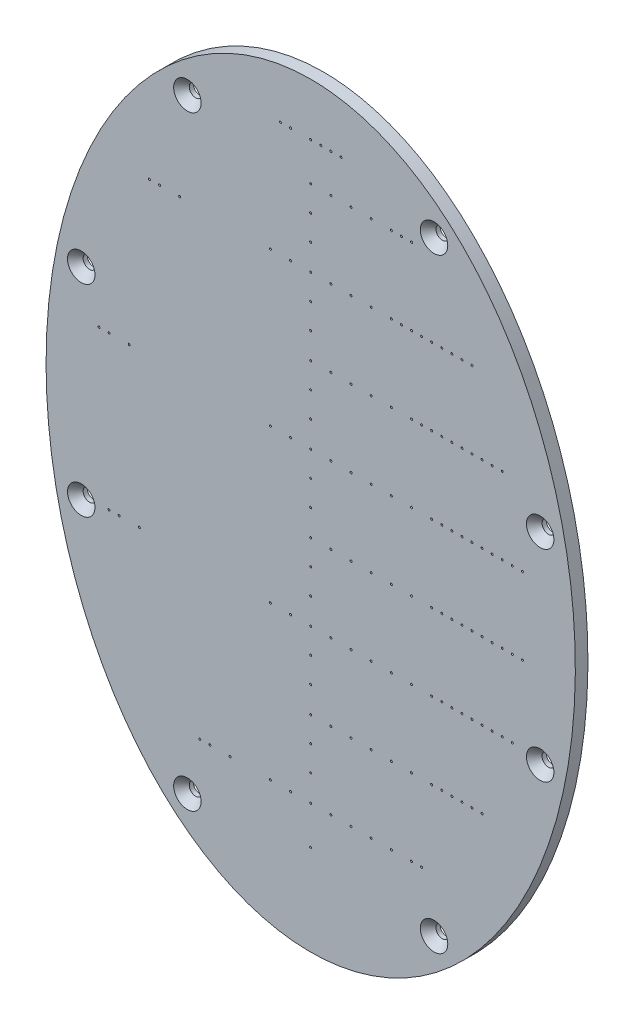
SolidWorks part; units mm, degrees
material "6061 Alloy"
ref_plane "Front Plane" through (0, 0, 0) normal (0, 0, 1) x (1, 0, 0)
ref_plane "Top Plane" through (0, 0, 0) normal (0, 1, 0) x (1, 0, 0)
ref_plane "Right Plane" through (0, 0, 0) normal (1, 0, 0) x (0, 0, -1)
sketch "Sketch2" plane through (0, 0, 0) normal (0, 0, 1) x (1, 0, 0)
  ellipse E0 centre (0, 0) end of major axis (0, 95.25) minor radius 66.675
  dimension "D1" = 190.5
  dimension "D2" = 133.35
extrude "Boss-Extrude1" add sketch "Sketch2" along normal blind 3.175
ref_plane "Plane1" through (0, 130.81, 0) normal (0, 1, 0) x (1, 0, 0)
hole_wizard "CSK for #4 Flat Head Socket Cap Screw1" positions "Sketch4" profile "Sketch3" countersink size "#4" standard "ANSI Inch"
sketch "Sketch4" plane through (0, 0, 3.175) normal (0, 0, 1) x (1, 0, 0)
  line L3 (0, 0) -> (31.0721, 76.2) construction
  ellipse E0 centre (0, 0) end of major axis (0, 88.9) minor radius 60.325
  ellipse E1 centre (0, 0) end of major axis (0, 95.25) minor radius 66.675 construction
  ellipse E2 centre (0, 0) end of major axis (0, 95.25) minor radius 66.675 construction
  point P2 (31.0721, 76.2)
  point P4 (57.8103, 25.4)
  point P13 (31.0721, -76.2)
  point P69 (57.8103, -25.4)
  dimension "D1" = 6.35
  dimension "D2" = 6.35
  dimension "D4" = 25.4
  dimension "D5" = 50.8
sketch "Sketch3" plane through (31.0721, 76.2, 3.175) normal (1, 0, 0) x (0, -1, 0)
  line L0 (0, 0) -> (0, 92.9286)
  line L1 (0, 92.9286) -> (1.6319, 91.948)
  line L2 (1.6319, 91.948) -> (1.6319, 2.1021)
  line L3 (1.6319, 2.1021) -> (3.4593, 0)
  line L5 (3.4593, 0) -> (0, 0)
  line L6 (-1.6319, 2.1021) -> (-3.4593, 0) construction
  line L10 (0, 92.9286) -> (-1.632, 91.948) construction
  line L11 (0, -6.35) -> (0, 107.95) construction
  dimension "Hole Dia." = 3.2639
  dimension "Hole Depth" = 91.948
  dimension "Near C'Sink Dia." = 6.9186
  dimension "Near C'Sink Angle" = 82
  dimension "Drill Angle" = 118
mirror "Mirror1" about plane through (0, 0, 0) normal (1, 0, 0) of "CSK for #4 Flat Head Socket Cap Screw1"
hole_wizard "CBORE for 1/2 Hex Head Bolt1" positions "Sketch8" profile "Sketch9" counterbore size "1/2" standard "ANSI Inch"
sketch "Sketch8" plane through (0, 0, 0) normal (0, 0, -1) x (-1, 0, 0)
  line L3 (0, 72.39) -> (0, 62.738) construction
  line L4 (0, 72.39) -> (0, 82.042) construction
  line L6 (0, 82.042) -> (-62.7225, 82.042) construction
  line L10 (0, 72.39) -> (-68.4113, 72.39) construction
  line L12 (0, 53.086) -> (-75.0551, 53.086) construction
  line L14 (0, 33.782) -> (-81.8919, 33.782) construction
  line L16 (0, 14.478) -> (-86.9631, 14.478) construction
  line L18 (0, -4.826) -> (-81.8919, -4.826) construction
  line L20 (0, -24.13) -> (-60.2195, -24.13) construction
  line L22 (0, -43.434) -> (-66.675, -43.434) construction
  line L24 (0, -62.738) -> (-65.3847, -62.738) construction
  line L25 (-5.08, 14.478) -> (-5.08, -116.9907) construction
  line L27 (-10.16, 14.478) -> (-10.16, -116.9907) construction
  line L29 (-15.24, -116.9907) -> (-15.24, 14.478) construction
  line L31 (-20.32, 14.478) -> (-20.32, -116.9907) construction
  line L33 (-25.4, -116.9907) -> (-25.4, 14.478) construction
  line L37 (-30.48, -116.9907) -> (-30.48, 14.478) construction
  line L39 (-33.02, 14.478) -> (-33.02, -116.9907) construction
  line L41 (-35.56, -116.9907) -> (-35.56, 14.478) construction
  line L43 (-38.1, 14.478) -> (-38.1, -116.9907) construction
  line L45 (-40.64, -116.9907) -> (-40.64, 14.478) construction
  line L47 (-43.18, 14.478) -> (-43.18, -116.9907) construction
  line L49 (-45.72, -116.9907) -> (-45.72, 14.478) construction
  line L51 (-48.26, 14.478) -> (-48.26, -116.9907) construction
  line L53 (-50.8, -116.9907) -> (-50.8, 14.478) construction
  line L55 (-53.34, 14.478) -> (-53.34, -116.9907) construction
  line L56 (0, 72.39) -> (0, 62.738) construction
  ellipse E0 centre (0, 0) end of major axis (0, 76.2) minor radius 57.15 construction
  point P0 (0, 72.39)
  point P37 (0, 53.086)
  point P39 (0, 33.782)
  point P41 (0, 14.478)
  point P43 (0, -4.826)
  point P45 (0, -24.13)
  point P47 (0, -43.434)
  point P49 (0, -62.738)
  point P50 (0, -72.39)
  point P54 (0, 82.042)
  point P109 (-5.08, 82.042)
  point P111 (-7.62, 82.042)
  point P116 (-2.54, 82.042)
  point P117 (-20.32, 72.39)
  point P121 (-15.24, 72.39)
  point P123 (-10.16, 72.39)
  point P125 (-5.08, 72.39)
  point P133 (-22.86, 72.39)
  point P136 (-5.08, 53.086)
  point P138 (-10.16, 53.086)
  point P140 (-15.24, 53.086)
  point P144 (-20.32, 53.086)
  point P146 (-22.86, 53.086)
  point P148 (-25.4, 53.086)
  point P150 (-27.94, 53.086)
  point P153 (-30.48, 53.086)
  point P155 (-33.02, 53.086)
  point P157 (-35.56, 53.086)
  point P160 (-38.1, 53.086)
  point P163 (-10.16, 33.782)
  point P165 (-15.24, 33.782)
  point P167 (-20.32, 33.782)
  point P171 (-25.4, 33.782)
  point P173 (-27.94, 33.782)
  point P175 (-30.48, 33.782)
  point P177 (-33.02, 33.782)
  point P179 (-35.56, 33.782)
  point P181 (-38.1, 33.782)
  point P183 (-40.64, 33.782)
  point P185 (-43.18, 33.782)
  point P187 (-45.72, 33.782)
  point P189 (-48.26, 33.782)
  point P195 (-5.08, 33.782)
  point P198 (-5.08, 14.478)
  point P200 (-10.16, 14.478)
  point P202 (-15.24, 14.478)
  point P204 (-20.32, 14.478)
  point P208 (-25.4, 14.478)
  point P212 (-30.48, 14.478)
  point P214 (-33.02, 14.478)
  point P216 (-35.56, 14.478)
  point P218 (-38.1, 14.478)
  point P220 (-40.64, 14.478)
  point P221 (-43.18, 14.478)
  point P223 (-45.72, 14.478)
  point P225 (-48.26, 14.478)
  point P227 (-50.8, 14.478)
  point P240 (-53.34, 14.478)
  point P287 (-5.08, -4.826)
  point P289 (-10.16, -4.826)
  point P291 (-15.24, -4.826)
  point P293 (-20.32, -4.826)
  point P295 (-25.4, -4.826)
  point P299 (-30.48, -4.826)
  point P301 (-33.02, -4.826)
  point P303 (-35.56, -4.826)
  point P305 (-38.1, -4.826)
  point P306 (-40.64, -4.826)
  point P308 (-43.18, -4.826)
  point P310 (-45.72, -4.826)
  point P312 (-48.26, -4.826)
  point P314 (-50.8, -4.826)
  point P316 (-53.34, -4.826)
  point P331 (-5.08, -24.13)
  point P333 (-10.16, -24.13)
  point P335 (-15.24, -24.13)
  point P336 (-20.32, -24.13)
  point P338 (-25.4, -24.13)
  point P342 (-30.48, -24.13)
  point P344 (-33.02, -24.13)
  point P346 (-35.56, -24.13)
  point P348 (-38.1, -24.13)
  point P350 (-40.64, -24.13)
  point P352 (-43.18, -24.13)
  point P354 (-45.72, -24.13)
  point P356 (-48.26, -24.13)
  point P360 (-50.8, -24.13)
  point P367 (-5.08, -43.434)
  point P369 (-10.16, -43.434)
  point P371 (-15.24, -43.434)
  point P373 (-20.32, -43.434)
  point P375 (-25.4, -43.434)
  point P379 (-30.48, -43.434)
  point P381 (-35.56, -43.434)
  point P383 (-38.1, -43.434)
  point P385 (-40.64, -43.434)
  point P387 (-43.18, -43.434)
  point P395 (-27.94, -62.738)
  point P397 (-25.4, -62.738)
  point P399 (-20.32, -62.738)
  point P401 (-15.24, -62.738)
  point P403 (-10.16, -62.738)
  point P405 (-5.08, -62.738)
  point P408 (-33.02, -43.434)
  point P411 (-40.64, 53.086)
  point P412 (-25.4, 72.39)
  point P422 (7.62, 82.042)
  point P424 (5.08, 82.042)
  point P427 (40.64, 53.086)
  point P429 (33.02, 53.086)
  point P432 (38.1, 53.086)
  point P434 (5.08, 53.086)
  point P436 (10.16, 53.086)
  point P440 (5.08, 14.478)
  point P442 (10.16, 14.478)
  point P444 (53.34, 14.478)
  point P446 (50.8, 14.478)
  point P448 (45.72, 14.478)
  point P453 (5.08, -24.13)
  point P455 (10.16, -24.13)
  point P457 (50.8, -24.13)
  point P459 (48.26, -24.13)
  point P461 (43.18, -24.13)
  point P465 (10.16, -62.738)
  point P467 (5.08, -62.738)
  point P469 (27.94, -62.738)
  point P471 (25.4, -62.738)
  point P473 (20.32, -62.738)
  point P490 (0, 62.738)
  point P491 (0, 43.434)
  point P492 (0, 24.13)
  point P493 (0, 4.826)
  point P494 (0, -14.478)
  point P495 (0, -33.782)
  point P496 (0, -53.086)
  point P500 (0, 66.04)
  point P502 (0, 59.69)
  point P514 (0, 46.736)
  point P515 (0, 40.386)
  point P516 (0, 27.432)
  point P517 (0, 21.082)
  point P518 (0, 8.128)
  point P519 (0, 1.778)
  point P520 (0, -11.176)
  point P521 (0, -17.526)
  point P522 (0, -30.48)
  point P523 (0, -36.83)
  point P524 (0, -49.784)
  point P525 (0, -56.134)
  dimension "D1" = 152.4
  dimension "D2" = 114.3
  dimension "D3" = 72.39
  dimension "D5" = 9.652
  dimension "D7" = 2.54
  dimension "D6" = 2.54
  dimension "D8" = 2.54
  dimension "D12" = 5.08
  dimension "D13" = 5.08
  dimension "D14" = 5.08
  dimension "D15" = 2.54
  dimension "D16" = 5.08
  dimension "D17" = 5.08
  dimension "D18" = 5.08
  dimension "D21" = 2.54
  dimension "D22" = 2.54
  dimension "D23" = 2.54
  dimension "D24" = 2.54
  dimension "D25" = 2.54
  dimension "D26" = 2.54
  dimension "D27" = 2.54
  dimension "D28" = 2.54
  dimension "D29" = 2.54
  dimension "D30" = 2.54
  dimension "D31" = 2.54
  dimension "D32" = 2.54
  dimension "D33" = 2.54
  dimension "D34" = 2.54
  dimension "D35" = 2.54
  dimension "D38" = 5.08
  dimension "D39" = 5.08
  dimension "D40" = 2.54
  dimension "D41" = 5.08
  dimension "D42" = 5.08
  dimension "D43" = 2.54
  dimension "D44" = 2.54
  dimension "D9" = 5.08
  dimension "D45" = 2.54
  dimension "D46" = 2.54
  dimension "D47" = 5.08
  dimension "D48" = 5.08
  dimension "D49" = 5.08
  dimension "D50" = 22.86
  dimension "D51" = 2.54
  dimension "D52" = 5.08
  dimension "D53" = 45.72
  dimension "D54" = 2.54
  dimension "D55" = 5.08
  dimension "D56" = 43.18
  dimension "D57" = 2.54
  dimension "D58" = 5.08
  dimension "D59" = 20.32
  dimension "D60" = 9.652
  dimension "D61" = 6.35
  dimension "D62" = 6.35
  dimension "D64" = 19.304
  dimension "D10" = 5.08
  dimension "D11" = 2.54
  dimension "D19" = 5.08
  dimension "D20" = 2.54
  dimension "D4" = 16
  dimension "D63" = 7
sketch "Sketch9" plane through (0, 72.39, 0) normal (1, 0, 0) x (0, 1, 0)
  line L0 (0, 0) -> (0, 6.5026)
  line L1 (0, 6.5026) -> (0.254, 6.35)
  line L2 (0.254, 6.35) -> (0.254, 1.5875)
  line L3 (0.254, 1.5875) -> (0.508, 1.5875)
  line L4 (0.508, 1.5875) -> (0.508, 0)
  line L5 (0.508, 0) -> (0, 0)
  line L10 (0, 6.5026) -> (-0.254, 6.35) construction
  line L11 (0, -6.35) -> (0, 107.95) construction
  dimension "Hole Dia." = 0.508
  dimension "Hole Depth" = 6.35
  dimension "C'Bore Dia." = 1.016
  dimension "C'Bore Depth" = 1.5875
  dimension "Drill Angle" = 118
sketch "Sketch10" plane through (0, 0, 3.175) normal (0, 0, 1) x (1, 0, 0)
  point P0 (0, 0)
equation "\"D6@Sketch8\"=\"D7@Sketch8\""
equation "\"D8@Sketch8\"=\"D7@Sketch8\""
equation "\"D10@Sketch8\"=\"D7@Sketch8\"*2"
equation "\"D11@Sketch8\"=\"D7@Sketch8\""
equation "\"D12@Sketch8\"=\"D7@Sketch8\"*2"
equation "\"D13@Sketch8\"=\"D7@Sketch8\"*2"
equation "\"D14@Sketch8\"=\"D7@Sketch8\"*2"
equation "\"D15@Sketch8\"=\"D7@Sketch8\""
equation "\"D16@Sketch8\"=\"D7@Sketch8\"*2"
equation "\"D17@Sketch8\"=\"D7@Sketch8\"*2"
equation "\"D18@Sketch8\"=\"D7@Sketch8\"*2"
equation "\"D19@Sketch8\"=\"D7@Sketch8\"*2"
equation "\"D20@Sketch8\"=\"D7@Sketch8\""
equation "\"D21@Sketch8\"=\"D7@Sketch8\""
equation "\"D22@Sketch8\"=\"D7@Sketch8\""
equation "\"D23@Sketch8\"=\"D7@Sketch8\""
equation "\"D24@Sketch8\"=\"D7@Sketch8\""
equation "\"D25@Sketch8\"=\"D7@Sketch8\""
equation "\"D26@Sketch8\"=\"D7@Sketch8\""
equation "\"D27@Sketch8\"=\"D7@Sketch8\""
equation "\"D28@Sketch8\"=\"D7@Sketch8\""
equation "\"D29@Sketch8\"=\"D7@Sketch8\""
equation "\"D30@Sketch8\"=\"D7@Sketch8\""
equation "\"D31@Sketch8\"=\"D7@Sketch8\""
equation "\"D32@Sketch8\"=\"D7@Sketch8\""
equation "\"D33@Sketch8\"=\"D7@Sketch8\""
equation "\"D34@Sketch8\"=\"D7@Sketch8\""
equation "\"D35@Sketch8\"=\"D7@Sketch8\""
equation "\"D38@Sketch8\"=\"D7@Sketch8\"*2"
equation "\"D39@Sketch8\"=\"D7@Sketch8\"*2"
equation "\"D40@Sketch8\"=\"D7@Sketch8\""
equation "\"D41@Sketch8\"=\"D7@Sketch8\"*2"
equation "\"D42@Sketch8\"=\"D7@Sketch8\"*2"
equation "\"D43@Sketch8\"=\"D7@Sketch8\""
equation "\"D44@Sketch8\"=\"D7@Sketch8\""
